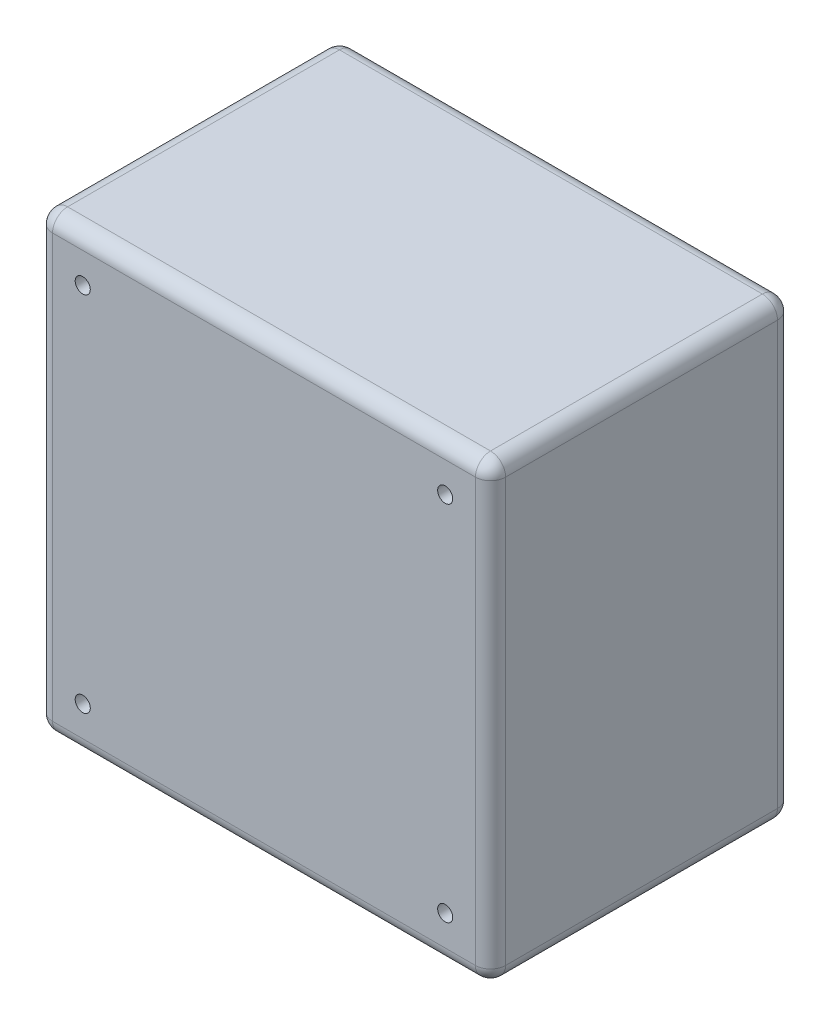
SolidWorks part; units mm, degrees
ref_plane "정면" through (0, 0, 0) normal (0, 0, 1) x (1, 0, 0)
ref_plane "윗면" through (0, 0, 0) normal (0, 1, 0) x (1, 0, 0)
ref_plane "우측면" through (0, 0, 0) normal (1, 0, 0) x (0, 0, -1)
sketch "스케치1" plane through (0, 0, 0) normal (0, 0, 1) x (1, 0, 0)
  line L0 (0, -75) -> (150, -75) construction
  line L1 (0, 0) -> (150, 0)
  line L2 (0, 0) -> (0, -150)
  line L3 (0, -150) -> (150, -150)
  line L4 (150, 0) -> (150, -150)
  line L5 (75, -150) -> (75, 0) construction
  circle A0 centre (15, -15) radius 2.5
  circle A1 centre (15, -135) radius 2.5
  circle A2 centre (135, -15) radius 2.5
  circle A3 centre (135, -135) radius 2.5
  dimension "D5" = 5
  dimension "D1" = 150
  dimension "D2" = 150
  dimension "D3" = 15
  dimension "D4" = 15
extrude "보스-돌출1" add sketch "스케치1" along normal blind 100
fillet "필렛1" radius 5 12 edges at (75, -150, 100) (75, -150, 0) (0, -75, 100) (0, -150, 50) (0, -75, 0) (75, 0, 100) (0, 0, 50) (75, 0, 0) (150, -150, 50) (150, -75, 100) (150, 0, 50) (150, -75, 0)
extrude "보스-돌출2" add sketch "스케치1<2>" against normal blind 8 separate body contours A1 | A3 | A2 | A0
sketch "스케치1<2>" plane through (0, 0, 0) normal (0, 0, 1) x (1, 0, 0) same geometry as "스케치1"
